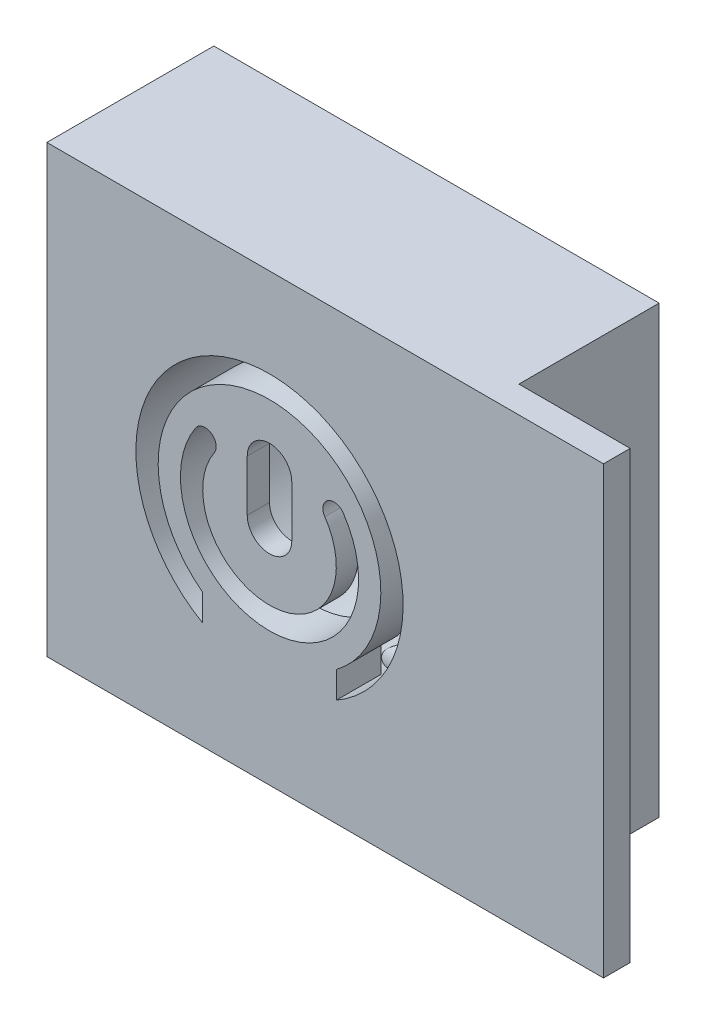
SolidWorks part; units mm, degrees
material "ABS"
ref_plane "Front Plane" through (0, 0, 0) normal (0, 0, 1) x (1, 0, 0)
ref_plane "Top Plane" through (0, 0, 0) normal (0, 1, 0) x (1, 0, 0)
ref_plane "Right Plane" through (0, 0, 0) normal (1, 0, 0) x (0, 0, -1)
sketch "Sketch1" plane through (0, 0, 0) normal (0, 0, 1) x (1, 0, 0)
  line L1 (-10, 10) -> (10, 10)
  line L2 (-10, 10) -> (-10, -10)
  line L3 (-10, -10) -> (10, -10)
  line L4 (10, 10) -> (10, -10)
  line L5 (-10, 10) -> (10, -10) construction
  line L6 (-10, -10) -> (10, 10) construction
  point P0 (0, 0)
  dimension "D1" = 20
  dimension "D2" = 20
extrude "Boss-Extrude1" add sketch "Sketch1" along normal blind 7.5
sketch "Sketch2" plane through (0, 0, 0) normal (0, 0, -1) x (-1, 0, 0)
  circle A0 centre (0, 0) radius 6
  dimension "D1" = 12
extrude "Cut-Extrude1" cut sketch "Sketch2" against normal blind 5.5
sketch "Sketch3" plane through (0, 0, 5.5) normal (0, 0, -1) x (-1, 0, 0)
  line L0 (-3, -4) -> (-3, -5.1962)
  line L1 (0, 6) -> (0, -6) construction
  line L2 (3, -4) -> (3, -5.1962)
  arc A0 (3, -5.1962) -> (-3, -5.1962) centre (0, 0) ccw
  circle A1 centre (0, 0) radius 5
  circle A2 centre (0, 0) radius 6 construction
  circle M5 centre (0, 0) radius 6
  dimension "D1" = 10
  dimension "D2" = 3
extrude "Cut-Extrude2" cut sketch "Sketch3" against normal blind 5 contours L1 A0 L0 A1 | L1 A1 L2 M5 region at (3.127, -4.5981, 5.5) region at (-0.127, 5.5, 5.5)
sketch "Sketch4" plane through (0, 0, 5.5) normal (0, 0, -1) x (-1, 0, 0)
  circle A0 centre (0, 0) radius 4
  dimension "D1" = 8
extrude "Cut-Extrude3" cut sketch "Sketch4" against normal blind 1
sketch "Sketch5" plane through (0, 0, 7.5) normal (0, 0, 1) x (1, 0, 0)
  line L0 (0, 2.3) -> (0, 0) construction
  line L1 (-1, 2.3) -> (-1, 0)
  line L2 (1, 2.3) -> (1, 0)
  arc A0 (-1, 2.3) -> (1, 2.3) centre (0, 2.3) cw
  arc A1 (-1, 0) -> (1, 0) centre (0, 0) ccw
  arc A2 (-2.4828, 1.684) -> (2.4828, 1.684) centre (0, 0) ccw
  arc A3 (-3.3104, 2.2453) -> (3.3104, 2.2453) centre (0, 0) ccw
  arc A4 (-2.4828, 1.684) -> (-3.3104, 2.2453) centre (-2.8966, 1.9647) ccw
  arc A5 (2.4828, 1.684) -> (3.3104, 2.2453) centre (2.8966, 1.9647) cw
  dimension "D4" = 3
  dimension "D5" = 2.3
  dimension "D1" = 1
  dimension "D2" = 1
  dimension "D3" = 1
extrude "Cut-Extrude4" cut sketch "Sketch5" against normal up to next
sketch "Sketch6" plane through (0, 0, 0) normal (0, 0, -1) x (-1, 0, 0)
  line L0 (0, 10) -> (0, -10) construction
  line L1 (6.5, 2.75) -> (8.5, 2.75)
  line L2 (6.5, 2.75) -> (6.5, -2.75)
  line L3 (6.5, -2.75) -> (8.5, -2.75)
  line L4 (8.5, 2.75) -> (8.5, -2.75)
  line L5 (6.5, 2.75) -> (8.5, -2.75) construction
  line L6 (6.5, -2.75) -> (8.5, 2.75) construction
  line L7 (-2.75, -6.5) -> (2.75, -6.5)
  line L8 (-2.75, -6.5) -> (-2.75, -8.5)
  line L9 (-2.75, -8.5) -> (2.75, -8.5)
  line L10 (2.75, -6.5) -> (2.75, -8.5)
  line L11 (-2.75, -6.5) -> (2.75, -8.5) construction
  line L12 (-2.75, -8.5) -> (2.75, -6.5) construction
  line L13 (-10, 10) -> (10, 10) construction
  line L14 (10, -10) -> (-10, -10) construction
  line L15 (-10, 0) -> (10, 0) construction
  line L16 (-10, -10) -> (-10, 10) construction
  line L17 (10, 10) -> (10, -10) construction
  point P0 (7.5, 0)
  point P5 (0, -7.5)
  dimension "D1" = 2
  dimension "D2" = 5.5
  dimension "D3" = 1.5
  dimension "D4" = 1.5
extrude "Cut-Extrude5" cut sketch "Sketch6" against normal blind 7
sketch "Sketch7" plane through (-10, 0, 0) normal (-1, 0, 0) x (0, 0, 1)
  line L0 (0, 0) -> (7.5, 0) construction
  line L1 (7.5, 10) -> (7.5, -10) construction
  circle A0 centre (3.75, 0) radius 1.5
  dimension "D1" = 3
extrude "Cut-Extrude6" cut sketch "Sketch7" against normal up to next
sketch "Sketch8" plane through (0, -10, 0) normal (0, -1, 0) x (-1, 0, 0)
  line L0 (0, -7.5) -> (0, 0) construction
  line L1 (10, -7.5) -> (-10, -7.5) construction
  line L2 (10, 0) -> (-10, 0) construction
  circle A0 centre (0, -3.75) radius 1.5
  dimension "D1" = 3
extrude "Cut-Extrude7" cut sketch "Sketch8" against normal up to next
sketch "Sketch9" plane through (10, 0, 0) normal (1, 0, 0) x (0, 0, -1)
  line L0 (0, 0) -> (-7.5, 0) construction
  line L1 (-7.5, -10) -> (-7.5, 10) construction
  line L2 (-3.75, 10) -> (-3.75, 0) construction
  line L3 (-7.5, 10) -> (0, 10) construction
  circle A0 centre (-3.75, 4) radius 1.8
  circle A1 centre (-3.75, -4) radius 1.8
  dimension "D1" = 3.6
  dimension "D2" = 4
extrude "Cut-Extrude8" cut sketch "Sketch9" against normal up to next
sketch "Sketch10" plane through (10, 0, 0) normal (1, 0, 0) x (0, 0, -1)
  line L0 (-7.5, -10) -> (0, -10) construction
  line L1 (-7.5, 10) -> (-6.3, 10)
  line L2 (-7.5, 10) -> (-7.5, -10)
  line L3 (-7.5, -10) -> (-6.3, -10)
  line L4 (-6.3, 10) -> (-6.3, -10)
  dimension "D1" = 1.2
extrude "Boss-Extrude2" add sketch "Sketch10" along normal blind 5
sketch "Sketch11" plane through (0, 0, 5.5) normal (0, 0, -1) x (-1, 0, 0)
  line L0 (0, 0) -> (0, 4.5) construction
  circle A0 centre (0, 4.5) radius 0.5
  arc A1 (3, -4) -> (-3, -4) centre (0, 0) ccw construction
  circle A2 centre (0, 0) radius 4 construction
extrude "Boss-Extrude3" add sketch "Sketch11" along normal blind 2
sketch "Sketch12" plane through (0, 0, 0) normal (0, 0, -1) x (-1, 0, 0)
  line L0 (0, 0) -> (0, 4.5) construction
  line L18 (-3.33, 6.575) -> (3.33, 6.575)
  line L19 (-3.33, 6.575) -> (-3.33, 2.425)
  line L20 (-3.33, 2.425) -> (3.33, 2.425)
  line L21 (3.33, 6.575) -> (3.33, 2.425)
  line L22 (-3.33, 6.575) -> (3.33, 2.425) construction
  line L23 (-3.33, 2.425) -> (3.33, 6.575) construction
  dimension "D1" = 6.66
  dimension "D2" = 4.15
extrude "Cut-Extrude9" cut sketch "Sketch12" against normal up to surface (3.5 mm away) up to face at (-0.5, 4.5, 3.5)
sketch "Sketch13" plane through (0, 0, 0) normal (0, 0, -1) x (-1, 0, 0)
  line L0 (3.33, 6.575) -> (3.33, 4.9911) construction
  line L1 (-3.33, 6.575) -> (3.33, 6.575)
  line L2 (-3.33, 6.575) -> (-3.33, 2.425)
  line L3 (-3.33, 2.425) -> (3.33, 2.425)
  line L4 (3.33, 6.575) -> (3.33, 2.425)
  line L5 (-5.33, 0.425) -> (5.33, 0.425)
  line L6 (5.33, 8.575) -> (5.33, 0.425)
  line L7 (-5.33, 8.575) -> (5.33, 8.575)
  line L8 (-5.33, 8.575) -> (-5.33, 0.425)
  dimension "D1" = 4.15
  dimension "D2" = 2
extrude "Boss-Extrude4" add sketch "Sketch13" along direction (0, 0, -1) on the side against the normal blind 2.5
